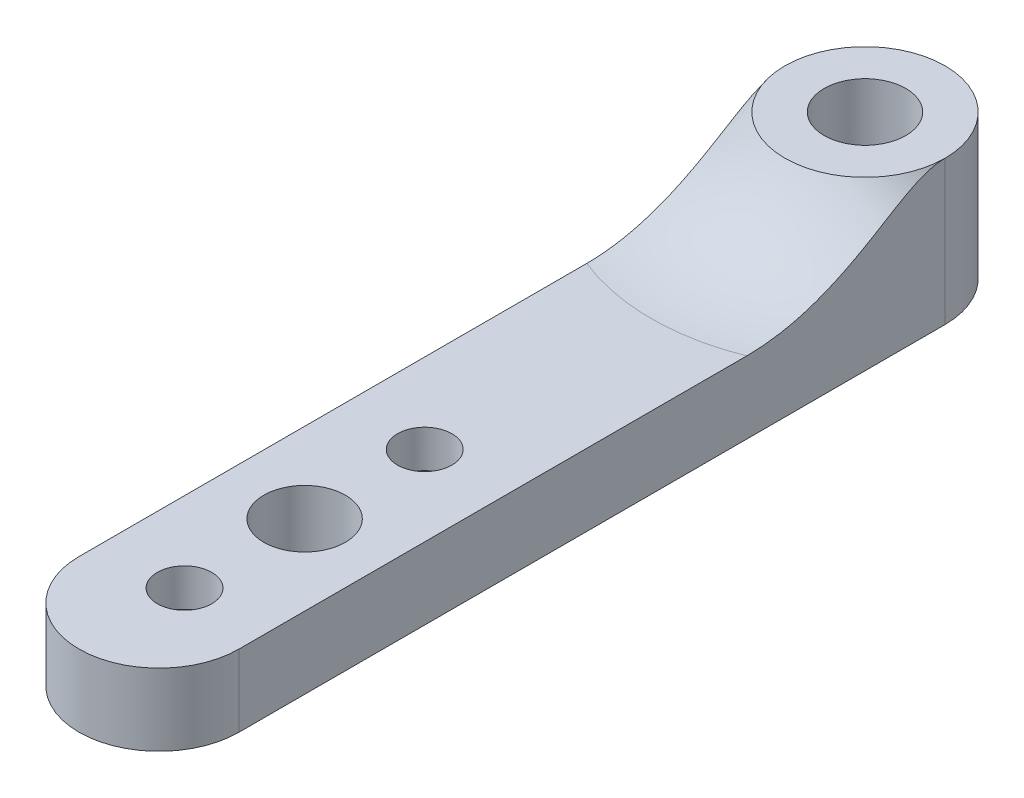
SolidWorks part; units mm, degrees
ref_plane "Front Plane" through (0, 0, 0) normal (0, 0, 1) x (1, 0, 0)
ref_plane "Top Plane" through (0, 0, 0) normal (0, 1, 0) x (1, 0, 0)
ref_plane "Right Plane" through (0, 0, 0) normal (1, 0, 0) x (0, 0, -1)
sketch "Sketch1" plane through (0, 0, 0) normal (0, 1, 0) x (1, 0, 0)
  line L2 (-5, -17.5) -> (-5, 17.5)
  line L4 (5, -17.5) -> (5, 17.5)
  line L5 (-5, -17.5) -> (5, 17.5) construction
  line L6 (-5, 17.5) -> (5, -17.5) construction
  arc A2 (-5, -17.5) -> (5, -17.5) centre (0, -17.5) ccw
  arc A3 (5, 17.5) -> (-5, 17.5) centre (0, 17.5) ccw
  point P0 (0, 0)
  dimension "D1" = 35
  dimension "D2" = 10
extrude "Boss-Extrude1" add sketch "Sketch1" along normal blind 4.5
ref_plane "Plane1" through (0, 4.5, 0) normal (0, 1, 0) x (1, 0, 0)
sketch "Sketch2" plane through (0, 4.5, 0) normal (0, 1, 0) x (1, 0, 0)
  circle A0 centre (0, 17.5) radius 2.55
  circle A1 centre (0, -17.5) radius 2.55
  arc A4 (5, 17.5) -> (-5, 17.5) centre (0, 17.5) ccw construction
  arc A5 (-5, -17.5) -> (5, -17.5) centre (0, -17.5) ccw construction
  dimension "D1" = 5.1
extrude "Cut-Extrude1" cut sketch "Sketch2" against normal through all
ref_plane "Plane2" through (0, 4.5, 0) normal (0, 1, 0) x (1, 0, 0)
sketch "Sketch3" plane through (0, 4.5, 0) normal (0, 1, 0) x (1, 0, 0)
  circle A0 centre (0, 17.5) radius 5
  arc A1 (5, 17.5) -> (-5, 17.5) centre (0, 17.5) ccw construction
extrude "Boss-Extrude2" add sketch "Sketch3" along normal blind 4.5
ref_plane "Plane3" through (0, 0, 0) normal (0, -1, 0) x (-1, 0, 0)
sketch "Sketch4" plane through (0, 0, 0) normal (0, -1, 0) x (-1, 0, 0)
  circle A0 centre (0, 17.5) radius 2.55
  circle A1 centre (0, 17.5) radius 2.55 construction
extrude "Cut-Extrude2" cut sketch "Sketch4" against normal through all
ref_plane "Plane4" through (0, 0, 0) normal (0, -1, 0) x (-1, 0, 0)
sketch "Sketch6" plane through (0, 0, 0) normal (0, -1, 0) x (-1, 0, 0)
  line L0 (-5, -17.5) -> (-5, -26.5946)
  line L1 (5, -17.5) -> (5, -26.5946)
  arc A0 (-5, -17.5) -> (5, -17.5) centre (0, -17.5) ccw
  arc A1 (-5, -26.5946) -> (5, -26.5946) centre (0, -26.5946) ccw
extrude "Boss-Extrude3" add sketch "Sketch6" against normal up to surface (4.5 mm away) up to face at (0, 4.5, 2.5)
ref_plane "Plane5" through (0, 0, 0) normal (0, -1, 0) x (-1, 0, 0)
sketch "Sketch7" plane through (0, 0, 0) normal (0, -1, 0) x (-1, 0, 0)
  line L0 (0, -17.5) -> (0, 49982.5) construction
  line L1 (0, -17.5) -> (8.8026, -17.5) construction
  point P10 (0, -10)
  point P11 (0, -25)
hole_wizard "CBORE for M3 SBHCS1" positions "Sketch10" profile "Sketch11" counterbore size "M3" standard "ANSI Metric" end condition up to next
sketch "Sketch10" plane through (0, 0, 0) normal (0, -1, 0) x (-1, 0, 0)
  point P0 (0, -10)
  point P3 (0, -25)
sketch "Sketch11" plane through (0, 0, 10) normal (1, 0, 0) x (0, 0, -1)
  line L0 (0, 0) -> (0, 4.5)
  line L1 (0, 4.5) -> (1.7, 4.5)
  line L3 (1.7, 4.5) -> (1.7, 2.15)
  line L4 (1.7, 2.15) -> (3.35, 2.15)
  line L5 (3.35, 2.15) -> (3.35, 0)
  line L7 (3.35, 0) -> (0, 0)
  line L11 (0, -6.35) -> (0, 107.95) construction
  dimension "Thru Hole Dia." = 3.4
  dimension "Thru Hole Depth" = 4.5
  dimension "C'Bore Dia." = 6.7
  dimension "C'Bore Depth" = 2.15
fillet "Fillet1" radius 10 1 edges at (0, 4.5, -12.5)
